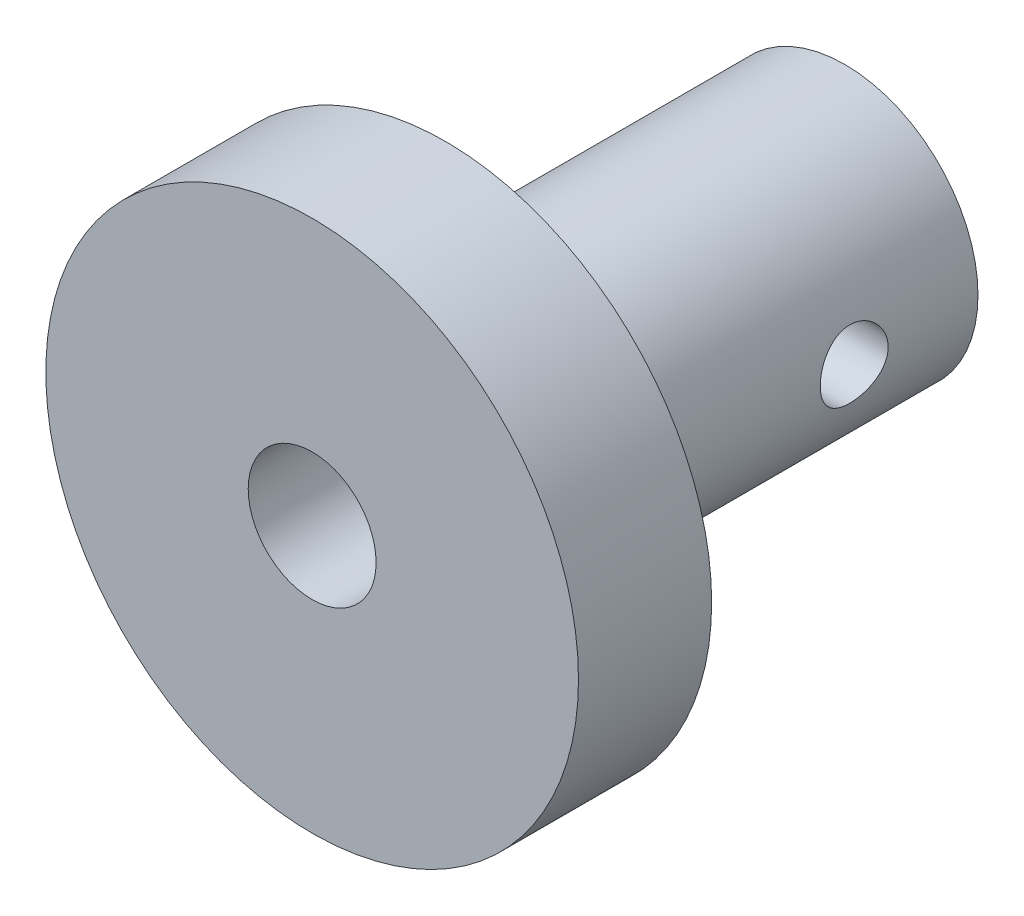
SolidWorks part; units mm, degrees
ref_plane "Front" through (0, 0, 0) normal (0, 0, 1) x (1, 0, 0)
ref_plane "Top" through (0, 0, 0) normal (0, 1, 0) x (1, 0, 0)
ref_plane "Right" through (0, 0, 0) normal (1, 0, 0) x (0, 0, -1)
sketch "Sketch3" plane through (0, 0, 0) normal (0, 0, 1) x (1, 0, 0)
  line L0 (0, -65.6804) -> (0, -71.4078) construction
  circle A0 centre (0, 0) radius 50.8
  circle A3 centre (0, 0) radius 12.1949
  dimension "D1" = 101.6
extrude "Boss-Extrude1" add sketch "Sketch3" along normal blind 25.4
sketch "Sketch4" plane through (0, 0, 0) normal (0, 0, -1) x (-1, 0, 0)
  circle A1 centre (0, 0) radius 25.4
  circle A2 centre (0, 0) radius 12.1949
  dimension "D1" = 50.8
extrude "Boss-Extrude2" add sketch "Sketch4" along normal blind 76.2
sketch "Sketch5" plane through (0, 0, 0) normal (1, 0, 0) x (0, 0, -1)
  circle A0 centre (52.5906, 0) radius 6.477
  dimension "D1" = 12.954
extrude "Cut-Extrude1" cut sketch "Sketch5" against normal through all both and the other way through all
